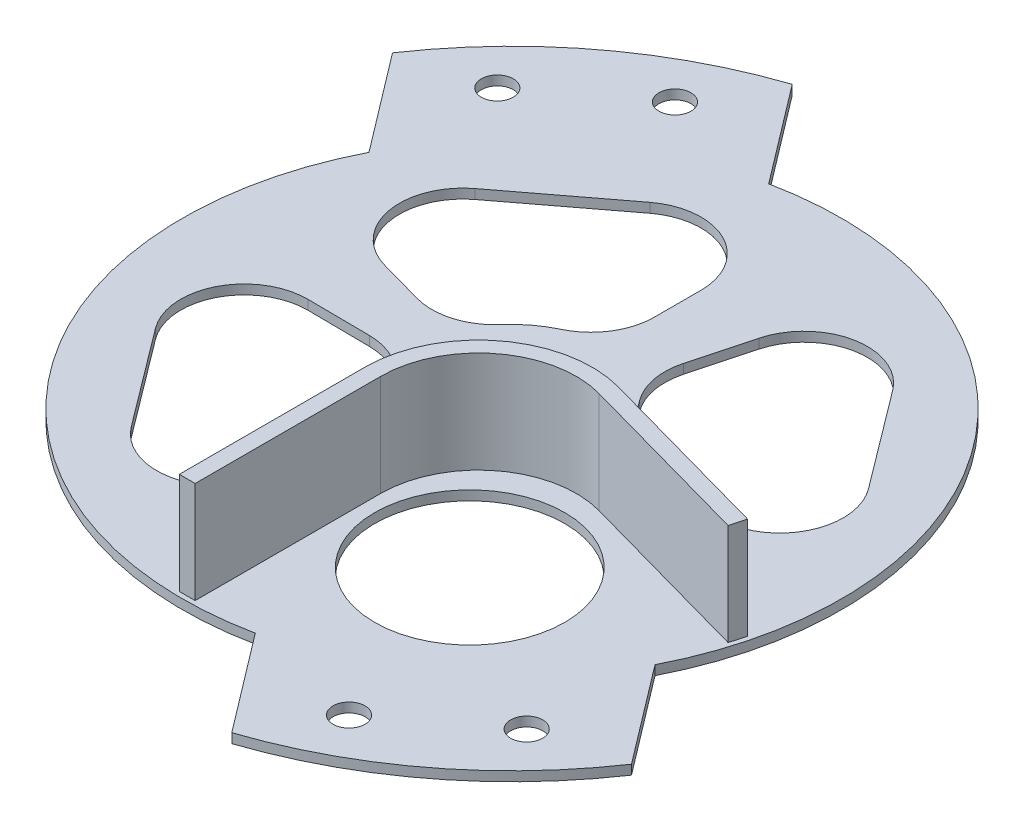
SolidWorks part; units mm, degrees
ref_plane "Alzado" through (0, 0, 0) normal (0, 0, 1) x (1, 0, 0)
ref_plane "Planta" through (0, 0, 0) normal (0, 1, 0) x (1, 0, 0)
ref_plane "Vista lateral" through (0, 0, 0) normal (1, 0, 0) x (0, 0, -1)
sketch "Croquis1" plane through (0, 0, 0) normal (0, 1, 0) x (1, 0, 0)
  circle A0 centre (0, 0) radius 140
  dimension "D1" = 280
extrude "Saliente-Extruir1" add sketch "Croquis1" along normal blind 3
sketch "Croquis3" plane through (0, 0, 0) normal (0, -1, 0) x (-1, 0, 0)
  line L0 (0, 0) -> (-60.6382, -82.6393) construction
  line L1 (2.5, -102.4695) -> (-2.5, -102.4695)
  line L2 (2.5, -102.4695) -> (2.5, -43.9289)
  line L3 (30.548, 11.0937) -> (98.0501, 29.8735)
  line L4 (-2.5, -102.4695) -> (-2.5, -43.9289)
  line L5 (-98.0501, -29.8735) -> (-41.6515, -14.1828)
  line L6 (98.0501, 29.8735) -> (2.5, 102.4695)
  line L7 (-42.9917, -9.3658) -> (-99.3903, -25.0565)
  line L8 (-99.3903, -25.0565) -> (-98.0501, -29.8735)
  line L9 (2.5, 102.4695) -> (2.5, 32.4037)
  line L10 (2.5, 32.4037) -> (30.548, 11.0937)
  line L11 (-12.2279, 30.1119) -> (-30.3893, 97.8915)
  line L12 (-30.3893, 97.8915) -> (-102.4812, 1.9605)
  line L13 (-102.4812, 1.9605) -> (-32.3934, 2.6298)
  line L14 (-32.3934, 2.6298) -> (-12.2279, 30.1119)
  line L15 (32.3934, -2.6298) -> (102.4812, -1.9605)
  line L16 (102.4812, -1.9605) -> (30.3893, -97.8915)
  line L17 (30.3893, -97.8915) -> (12.2279, -30.1119)
  line L18 (12.2279, -30.1119) -> (32.3934, -2.6298)
  circle A0 centre (0, 0) radius 32.5
  circle A1 centre (0, 0) radius 102.5
  circle A2 centre (-36.766, -50.1057) radius 30
  arc A3 (-2.5, -43.9289) -> (-41.6515, -14.1828) centre (-33.3758, -43.9289) ccw
  arc A4 (2.5, -43.9289) -> (-42.9917, -9.3658) centre (-33.3758, -43.9289) ccw
  circle A5 centre (0, 0) radius 13.2
  circle A6 centre (0, 0) radius 44 construction
  dimension "D1" = 205
  dimension "D3" = 60
  dimension "D9" = 65
  dimension "D13" = 26.4
  dimension "D14" = 88
  dimension "D2" = 5
  dimension "D4" = 5
  dimension "D5" = 15
  dimension "D6" = 15
  dimension "D7" = 15
  dimension "D8" = 15
  dimension "D10" = 120
  dimension "D11" = 120
  dimension "D12" = 120
extrude "Saliente-Extruir2" add sketch "Croquis3" against normal blind 35 contours L4 A3 L5 L8 L7 A4 L2 L1
extrude "Cortar-Extruir3" cut sketch "Croquis3<5>" against normal blind 150 contours L9 L10 L3 L6 | A2 | L15 L16 L17 L18 | L11 L12 L13 L14 | A5 region at (-37.0219, 0, -48.7279)
sketch "Croquis3<5>" plane through (0, 0, 0) normal (0, -1, 0) x (-1, 0, 0) same geometry as "Croquis3"
hole_wizard "Taladro de margen para 3/81" positions "Croquis5" profile "Croquis4" hole size "3/8" standard "Ansi Inch" end condition up to next
sketch "Croquis5" plane through (0, 3, 0) normal (0, 1, 0) x (1, 0, 0)
  line L0 (0, 0) -> (73.9724, -97.3617) construction
  line L1 (58.0474, -109.461) -> (89.8974, -85.2624) construction
  line L2 (0, 0) -> (58.0474, -109.461) construction
  line L3 (0, 0) -> (-84.6953, 111.4751) construction
  line L4 (-58.0474, 109.461) -> (0, 0) construction
  line L8 (-2.5, 102.4695) -> (-98.0501, 29.8735) construction
  circle A0 centre (0, 0) radius 140 construction
  point P13 (58.0474, -109.461)
  point P17 (89.8974, -85.2624)
  point P49 (-58.0474, 109.461)
  point P50 (-89.8974, 85.2624)
  dimension "D1" = 2
  dimension "D2" = 123.9
  dimension "D3" = 40
  dimension "D4" = 20
  dimension "D5" = 20
  dimension "D6" = 123.9
  dimension "D7" = 123.9
  dimension "D8" = 123.9
sketch "Croquis4" plane through (58.0474, 3, 109.461) normal (1, 0, 0) x (0, 0, 1)
  line L0 (0, 0) -> (0, 3)
  line L1 (0, 3) -> (5.0419, 3)
  line L2 (5.0419, 3) -> (5.0419, 0)
  line L5 (5.0419, 0) -> (0, 0)
  line L11 (0, -6.35) -> (0, 107.95) construction
  dimension "Diámetro de taladro hasta el siguiente" = 10.0838
  dimension "Profundidad de taladro hasta el siguiente" = 3
sketch "Croquis6" plane through (0, 3, 0) normal (0, 1, 0) x (1, 0, 0)
  line L0 (-92.5532, 47.4333) -> (-138.1404, 107.4347)
  line L1 (0, 0) -> (-84.6953, 111.4751) construction
  line L2 (-66.4778, 161.8817) -> (-20.8906, 101.8802)
  line L3 (20.8906, -101.8802) -> (66.4778, -161.8817)
  line L4 (0, 0) -> (38.2116, -50.2937) construction
  line L5 (92.5532, -47.4333) -> (138.1404, -107.4347)
  line L8 (-2.5, 102.4695) -> (-98.0501, 29.8735) construction
  arc A0 (138.1404, -107.4347) -> (-66.4778, 161.8817) centre (0, 0) ccw
  arc A1 (-92.5532, 47.4333) -> (20.8906, -101.8802) centre (0, 0) ccw
  arc A2 (-138.1404, 107.4347) -> (66.4778, -161.8817) centre (0, 0) ccw
  arc A5 (92.5532, -47.4333) -> (-20.8906, 101.8802) centre (0, 0) ccw
  circle A6 centre (0, 0) radius 140 construction
  dimension "D1" = 208
  dimension "D2" = 350
  dimension "D3" = 45
  dimension "D4" = 90
  dimension "D5" = 45
  dimension "D6" = 90
extrude "Cortar-Extruir4" cut sketch "Croquis6" against normal blind 10
fillet "Redondeo1" radius 20 12 edges at (-32.3934, 1.5, 2.6298) (-12.2279, 1.5, 30.1119) (-102.4812, 1.5, 1.9605) (-30.3893, 1.5, 97.8915) (32.3934, 1.5, -2.6298) (102.4812, 1.5, -1.9605) (30.3893, 1.5, -97.8915) (12.2279, 1.5, -30.1119) (-30.548, 1.5, -11.0937) (-2.5, 1.5, -32.4037) (-2.5, 1.5, -102.4695) (-98.0501, 1.5, -29.8735)
sketch "Croquis7" plane through (0, 0, 0) normal (0, -1, 0) x (1, 0, 0)
  circle A0 centre (0, 0) radius 15
  dimension "D1" = 30
extrude "Cortar-Extruir5" cut sketch "Croquis7" against normal blind 3
scale "Escala1" scale about centroid uniform scaling yes scale factor 1.15
